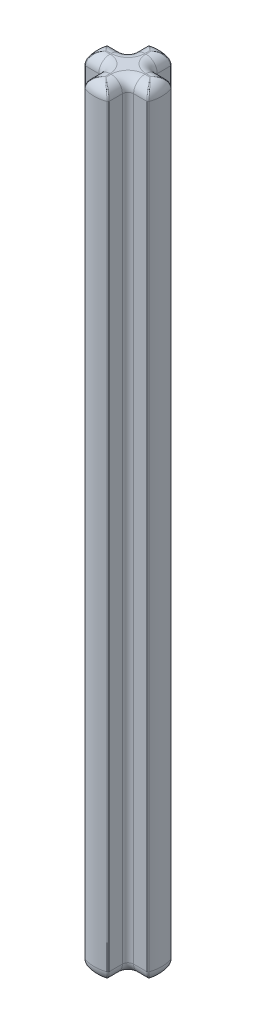
SolidWorks part; units mm, degrees
ref_plane "Front Plane" through (0, 0, 0) normal (0, 0, 1) x (1, 0, 0)
ref_plane "Top Plane" through (0, 0, 0) normal (0, 1, 0) x (1, 0, 0)
ref_plane "Right Plane" through (0, 0, 0) normal (1, 0, 0) x (0, 0, -1)
sketch "Sketch2" plane through (0, 0, 0) normal (0, 1, 0) x (1, 0, 0)
  line L0 (-0.84, -1.24) -> (-0.84, -2.1777)
  line L2 (-0.84, 2.1777) -> (-0.84, 1.24)
  line L4 (0.84, 2.1777) -> (0.84, 1.24)
  line L5 (-0.84, 2.2482) -> (0.84, -2.2482) construction
  line L6 (-0.84, -2.2482) -> (0.84, 2.2482) construction
  line L7 (-2.1777, 0.84) -> (-1.24, 0.84)
  line L9 (-2.1777, -0.84) -> (-1.24, -0.84)
  line L11 (-2.2482, 0.84) -> (2.2482, -0.84) construction
  line L12 (-2.2482, -0.84) -> (2.2482, 0.84) construction
  line L13 (1.24, 0.84) -> (2.1777, 0.84)
  line L14 (0.84, -1.24) -> (0.84, -2.1777)
  line L15 (1.24, -0.84) -> (2.1777, -0.84)
  arc A0 (0.7722, 2.2724) -> (-0.7722, 2.2724) centre (0, 0) ccw
  arc A1 (-2.2724, 0.7722) -> (-2.2724, -0.7722) centre (0, 0) ccw
  arc A2 (2.2724, -0.7722) -> (2.2724, 0.7722) centre (0, 0) ccw
  arc A3 (-0.7722, -2.2724) -> (0.7722, -2.2724) centre (0, 0) ccw
  arc A4 (-2.1777, 0.84) -> (-2.2724, 0.7722) centre (-2.1777, 0.74) ccw
  arc A5 (-2.2724, -0.7722) -> (-2.1777, -0.84) centre (-2.1777, -0.74) ccw
  arc A6 (-0.84, -2.1777) -> (-0.7722, -2.2724) centre (-0.74, -2.1777) ccw
  arc A7 (0.7722, -2.2724) -> (0.84, -2.1777) centre (0.74, -2.1777) ccw
  arc A8 (2.1777, -0.84) -> (2.2724, -0.7722) centre (2.1777, -0.74) ccw
  arc A9 (2.1777, 0.84) -> (2.2724, 0.7722) centre (2.1777, 0.74) cw
  arc A10 (0.7722, 2.2724) -> (0.84, 2.1777) centre (0.74, 2.1777) cw
  arc A11 (-0.7722, 2.2724) -> (-0.84, 2.1777) centre (-0.74, 2.1777) ccw
  arc A12 (-0.84, -1.24) -> (-1.24, -0.84) centre (-1.24, -1.24) ccw
  arc A13 (0.84, -1.24) -> (1.24, -0.84) centre (1.24, -1.24) cw
  arc A14 (1.24, 0.84) -> (0.84, 1.24) centre (1.24, 1.24) cw
  arc A15 (-1.24, 0.84) -> (-0.84, 1.24) centre (-1.24, 1.24) ccw
  point P42 (0.84, -0.84)
  dimension "D1" = 4.8
  dimension "D4" = 0.1
  dimension "D5" = 0.4
  dimension "D2" = 1.68
  dimension "D3" = 1.68
extrude "Boss-Extrude1" add sketch "Sketch2" along normal blind 55.2
fillet "Fillet1" radius 0.8 24 edges at (0.8213, 55.2, -2.2359) (0.84, 55.2, -1.7089) (0.9572, 55.2, -0.9572) (1.7089, 55.2, -0.84) (2.2359, 55.2, -0.8213) (2.4, 55.2, 0) (2.2359, 55.2, 0.8213) (1.7089, 55.2, 0.84) (0.9572, 55.2, 0.9572) (0.84, 55.2, 1.7089) (0.8213, 55.2, 2.2359) (0, 55.2, 2.4) (-0.8213, 55.2, 2.2359) (-0.84, 55.2, 1.7089) (-0.9572, 55.2, 0.9572) (-1.7089, 55.2, 0.84) (-2.2359, 55.2, 0.8213) (-2.4, 55.2, 0) (-2.2359, 55.2, -0.8213) (-1.7089, 55.2, -0.84) (-0.9572, 55.2, -0.9572) (-0.84, 55.2, -1.7089) (-0.8213, 55.2, -2.2359) (0, 55.2, -2.4)
fillet "Fillet2" radius 0.8 24 edges at (0.8213, 0, -2.2359) (0.84, 0, -1.7089) (0.9572, 0, -0.9572) (1.7089, 0, -0.84) (2.2359, 0, -0.8213) (2.4, 0, 0) (2.2359, 0, 0.8213) (1.7089, 0, 0.84) (0.9572, 0, 0.9572) (0.84, 0, 1.7089) (0.8213, 0, 2.2359) (0, 0, 2.4) (-0.8213, 0, 2.2359) (-0.84, 0, 1.7089) (-0.9572, 0, 0.9572) (-1.7089, 0, 0.84) (-2.2359, 0, 0.8213) (-2.4, 0, 0) (-2.2359, 0, -0.8213) (-1.7089, 0, -0.84) (-0.9572, 0, -0.9572) (-0.84, 0, -1.7089) (-0.8213, 0, -2.2359) (0, 0, -2.4)
